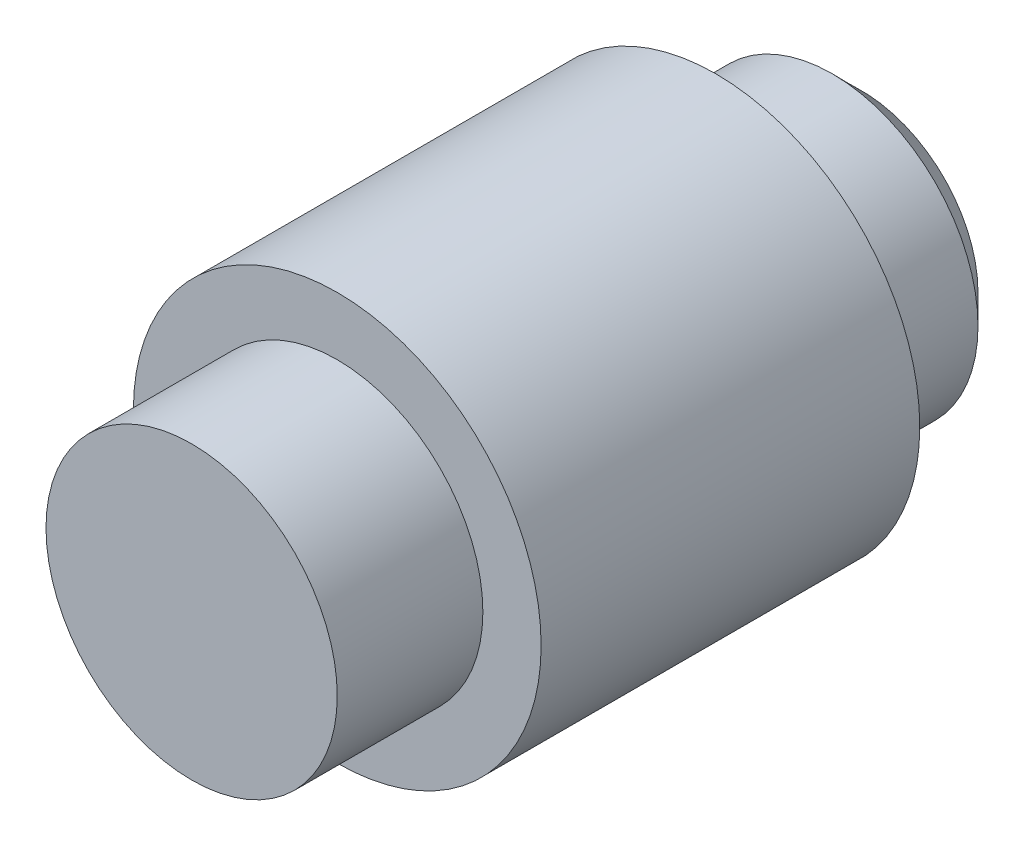
SolidWorks part; units mm, degrees
ref_plane "Front Plane" through (0, 0, 0) normal (0, 0, 1) x (1, 0, 0)
ref_plane "Top Plane" through (0, 0, 0) normal (0, 1, 0) x (1, 0, 0)
ref_plane "Right Plane" through (0, 0, 0) normal (1, 0, 0) x (0, 0, -1)
sketch "Sketch2" plane through (0, 0, 0) normal (0, 0, 1) x (1, 0, 0)
  circle A0 centre (0, 0) radius 1.25
  dimension "D1" = 2.5
sketch "Sketch3" plane through (0, 0, 0) normal (0, 0, 1) x (1, 0, 0)
  line L5 (-3.5, 3.5) -> (3.5, 3.5) construction
  line L6 (-3.5, 3.5) -> (-3.5, -3.5) construction
  line L7 (-3.5, -3.5) -> (3.5, -3.5) construction
  line L8 (3.5, 3.5) -> (3.5, -3.5) construction
  circle A0 centre (0, 0) radius 3.5
  point P4 (0, 3.5)
  point P6 (-3.5, 0)
  dimension "D1" = 7
extrude "Boss-Extrude1" add sketch "Sketch3" along normal blind 6.5
sketch "Sketch4" plane through (0, 0, 0) normal (0, 0, 1) x (1, 0, 0)
  circle A0 centre (0, 0) radius 2.5
  dimension "D1" = 5
extrude "Boss-Extrude2" add sketch "Sketch4" against normal blind 2.5
sketch "Sketch5" plane through (0, 0, 6.5) normal (0, 0, 1) x (1, 0, 0)
  circle A0 centre (0, 0) radius 2.5
  dimension "D1" = 5
extrude "Boss-Extrude3" add sketch "Sketch5" along normal blind 2.5
chamfer "Chamfer1" distance 0.5 angle 45 1 edges at (2.5, 0, -2.5)
equation "\"length\"=6.5"
equation "\"D1@Boss-Extrude1\"=\"length\""
equation "\"hole\"=5"
equation "\"D1@Sketch5\"=\"hole\""
equation "\"D1@Sketch4\"=\"hole\""
